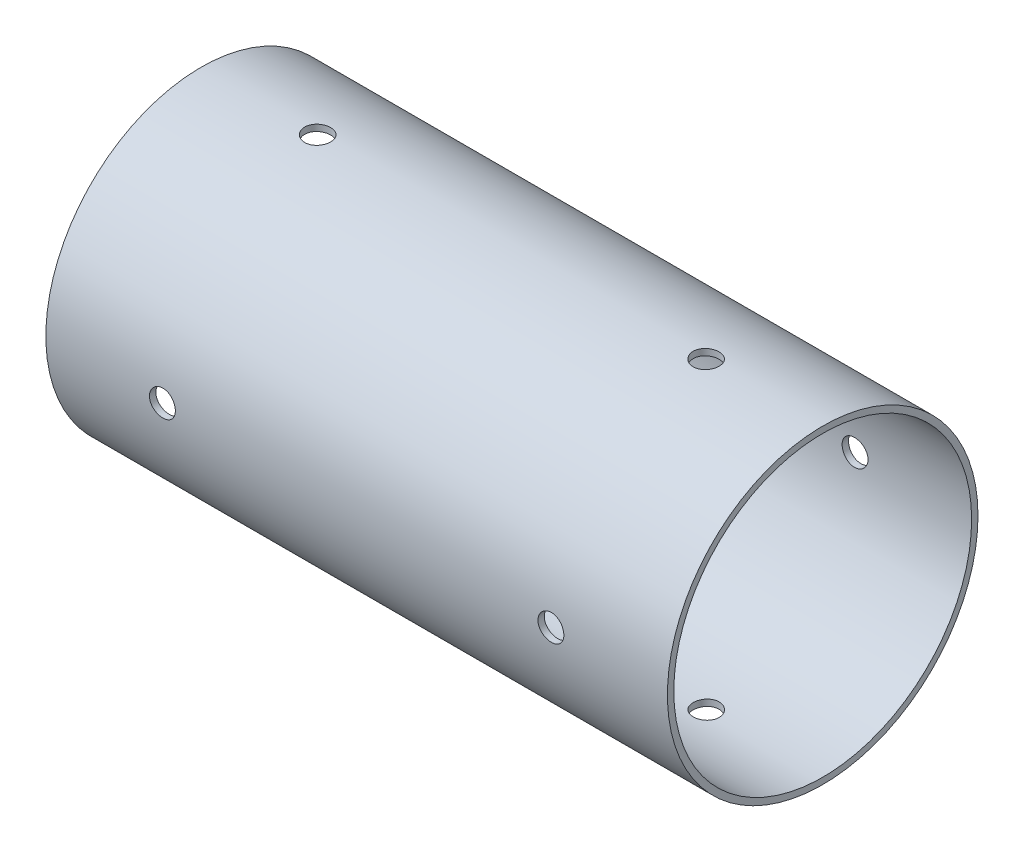
SolidWorks part; units mm, degrees
ref_plane "Front Plane" through (0, 0, 0) normal (1, 0, 0) x (0, 1, 0)
ref_plane "Top Plane" through (0, 0, 0) normal (0, 0, 1) x (0, 1, 0)
ref_plane "Right Plane" through (0, 0, 0) normal (0, 1, 0) x (-1, 0, 0)
sketch "Sketch1" plane through (0, 0, 0) normal (1, 0, 0) x (0, 1, 0)
  circle A0 centre (0, 0) radius 36.5125
  circle A1 centre (0, 0) radius 38.0746
  dimension "D1" = 73.025
  dimension "D2" = 76.1492
extrude "Boss-Extrude1" add sketch "Sketch1" along normal blind 152.4
sketch "Sketch3" plane through (0, 0, 0) normal (0, 1, 0) x (-1, 0, 0)
  line L0 (-152.4, 38.0746) -> (-152.4, -38.0746) construction
  circle A0 centre (-123.825, 0) radius 3.175
  point P4 (-123.825, 0)
  point P5 (0, 0)
  point P6 (-123.825, 0)
  dimension "D2" = 6.35
  dimension "D1" = 28.575
extrude "Cut-Extrude1" cut sketch "Sketch3" along normal through all
pattern_circular "CirPattern1" count 4 over 360 about axis through (152.4, 0, 0) along (-1, 0, 0) of "Cut-Extrude1"
sketch "Sketch4" plane through (0, 0, 0) normal (0, 1, 0) x (-1, 0, 0)
  circle A0 centre (-28.575, 0) radius 3.175
  point P2 (0, 0)
  dimension "D1" = 6.35
  dimension "D2" = 28.575
extrude "Cut-Extrude2" cut sketch "Sketch4" along normal through all
pattern_circular "CirPattern2" count 4 over 360 about axis through (152.4, 0, 0) along (-1, 0, 0) of "Cut-Extrude2" reverse direction yes
